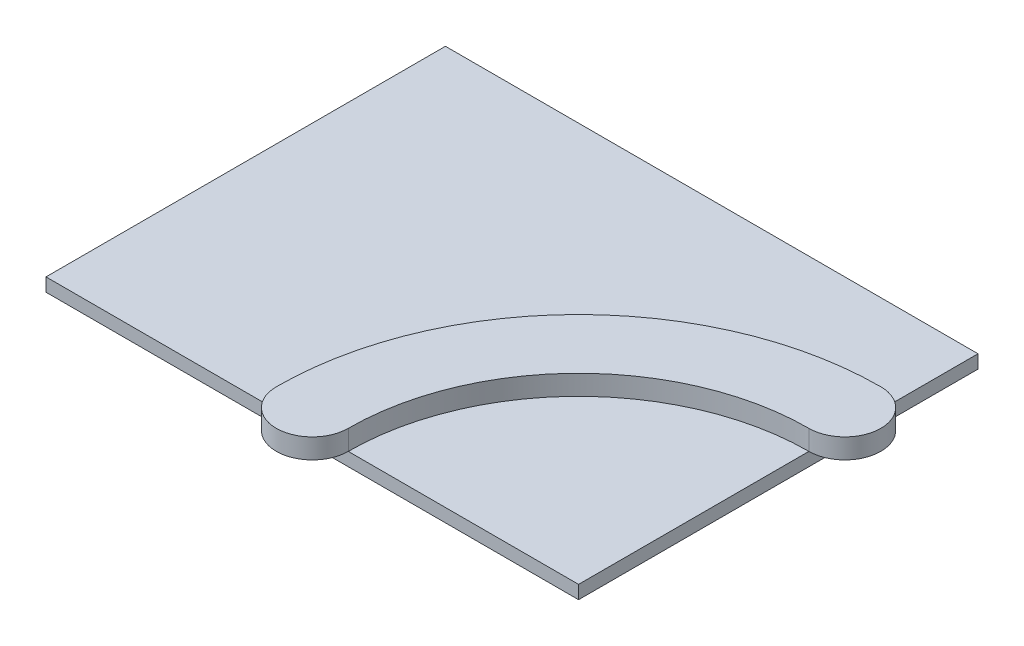
SolidWorks part; units mm, degrees
ref_plane "Front Plane" through (0, 0, 0) normal (0, 0, 1) x (1, 0, 0)
ref_plane "Top Plane" through (0, 0, 0) normal (0, 1, 0) x (1, 0, 0)
ref_plane "Right Plane" through (0, 0, 0) normal (1, 0, 0) x (0, 0, -1)
sketch "Sketch2" plane through (0, 0, 0) normal (0, 1, 0) x (1, 0, 0)
  line L1 (0, 0) -> (-400, 0)
  line L2 (0, 0) -> (0, 300)
  line L3 (0, 300) -> (-400, 300)
  line L4 (-400, 0) -> (-400, 300)
  dimension "D1" = 300
  dimension "D2" = 400
extrude "Boss-Extrude1" add sketch "Sketch2" along normal blind 10
sketch "Sketch3" plane through (0, 10, 0) normal (0, 1, 0) x (1, 0, 0)
  line L1 (-400, 0) -> (0, 0) construction
  line L2 (0, 0) -> (0, 300) construction
  arc A0 (-200, 0) -> (0, 200) centre (0, 0) cw construction
  arc A1 (0, 227.0196) -> (-227.0196, 0) centre (0, 0) ccw
  arc A2 (0, 172.9804) -> (-172.9804, 0) centre (0, 0) ccw
  arc A3 (0, 172.9804) -> (0, 227.0196) centre (0, 200) ccw
  arc A4 (-227.0196, 0) -> (-172.9804, 0) centre (-200, 0) ccw
  point P4 (-141.4214, 141.4214)
  point P11 (0, 0)
extrude "Boss-Extrude2" add sketch "Sketch3" along normal blind 15 separate body
